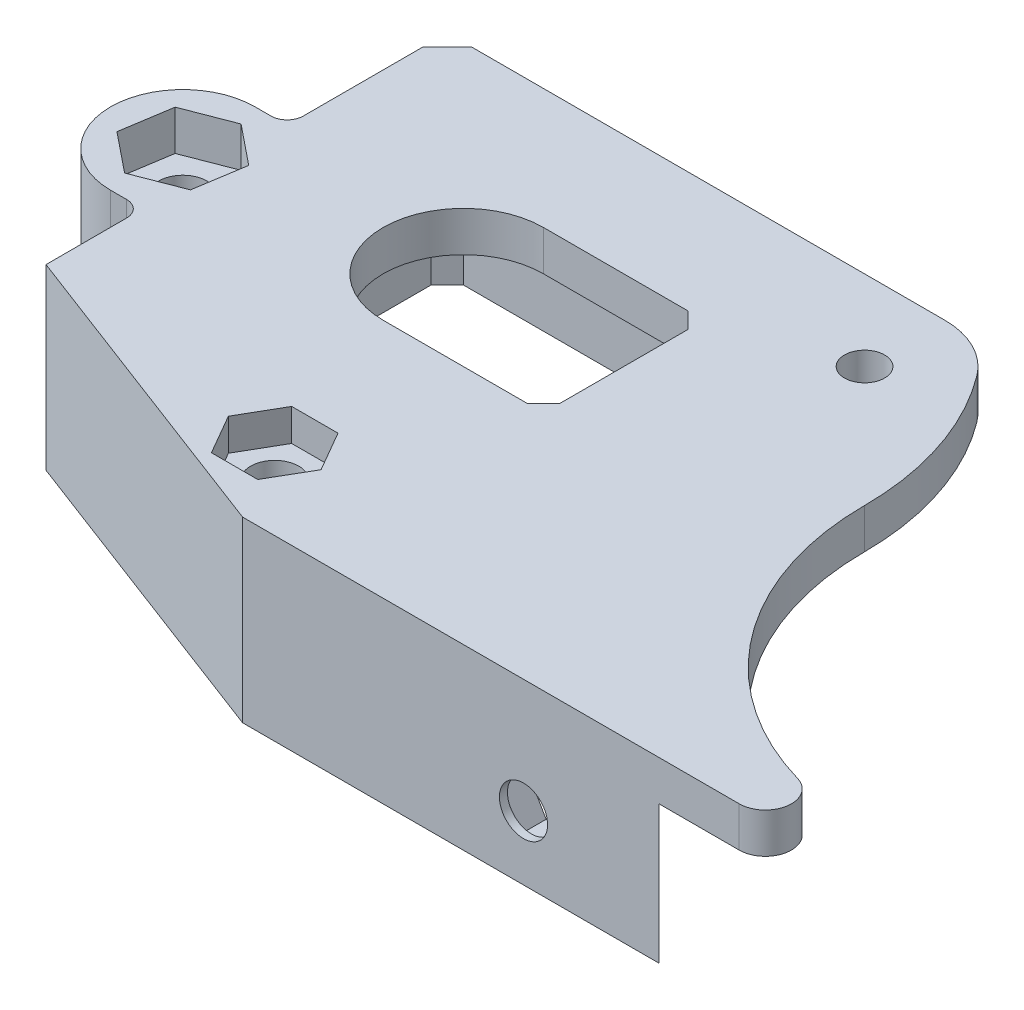
SolidWorks part; units mm, degrees
ref_plane "Front Plane" through (0, 0, 0) normal (0, 0, 1) x (1, 0, 0)
ref_plane "Top Plane" through (0, 0, 0) normal (0, 1, 0) x (1, 0, 0)
ref_plane "Right Plane" through (0, 0, 0) normal (1, 0, 0) x (0, 0, -1)
sketch "Sketch2" plane through (0, 0, 0) normal (0, 1, 0) x (1, 0, 0)
  line L0 (0, -40) -> (-72.5, -40) construction
  line L6 (-112, 25) -> (-112, -25)
  line L9 (-72.5, -40) -> (-20.6155, -40)
  line L10 (-102, 21) -> (-60, 21) construction
  line L11 (-102, 21) -> (-102, -21) construction
  line L12 (-102, -21) -> (-60, -21) construction
  line L13 (-60, 21) -> (-60, -21) construction
  line L14 (-102, 21) -> (-60, -21) construction
  line L21 (-102, -21) -> (-60, 21) construction
  line L22 (-29.4788, -34) -> (-77.0327, -34)
  line L23 (-108, -22.2403) -> (-108, 21)
  line L24 (-108, 21) -> (-60, 21)
  line L25 (-72.5, -40) -> (-112, -25)
  line L26 (-77.0327, -34) -> (-108, -22.2403)
  line L27 (-112, 25) -> (-56, 25)
  arc A2 (-22.016, 33.3961) -> (0, -40) centre (0, 0) cw construction
  arc A3 (-22.016, 33.3961) -> (-60, 21) centre (-63.6326, 96.5245) cw construction
  circle A8 centre (0, 0) radius 40 construction
  arc A9 (-20.6155, -40) -> (-29.4788, -34) centre (0, 0) cw
  circle A10 centre (-50, 15) radius 11 construction
  arc A11 (-60, 21) -> (-56, 25) centre (-50, 15) cw
  point P9 (-81, 0)
  point P20 (-112, 0)
  dimension "D1" = 40
  dimension "D2" = 72.5
  dimension "D6" = 45
  dimension "D11" = 15
  dimension "D14" = 4
  dimension "D9" = 22
  dimension "D3" = 42
  dimension "D4" = 42
  dimension "D5" = 81
  dimension "D7" = 6
  dimension "D8" = 4
  dimension "D10" = 50
  dimension "D12" = 4
  dimension "D13" = 50
  dimension "D15" = 52
extrude "Boss-Extrude1" add sketch "Sketch2" along normal blind 17.2
chamfer "Chamfer1" distance 3 angle 45 1 edges at (-112, 8.6, -25)
chamfer "Chamfer2" distance 2 angle 45 1 edges at (-108, 8.6, -21)
sketch "Sketch3" plane through (0, 17.2, 0) normal (0, 1, 0) x (1, 0, 0)
  line L0 (-85, 10) -> (-65, 10)
  line L1 (-72.5, -40) -> (-20.6155, -40)
  line L2 (-20.6155, -40) -> (-10.6155, -40)
  line L3 (-65, -10) -> (-85, -10)
  line L4 (-50, 25) -> (-109, 25)
  line L5 (-112, 22) -> (-112, -25)
  line L6 (-72.5, -40) -> (0, -40) construction
  line L7 (-112, -25) -> (-72.5, -40)
  line L8 (-109, 25) -> (-112, 22)
  line L9 (-65, 10) -> (-65, -10)
  circle A0 centre (-50, 15) radius 2.5
  arc A1 (0, -40) -> (-23.5728, 32.316) centre (0, 0) ccw construction
  arc A2 (-85, 10) -> (-85, -10) centre (-85, 0) ccw
  circle A3 centre (-78.5, -30) radius 3
  arc A4 (-35, 0) -> (-9.7132, -33.6252) centre (0, 0) ccw
  arc A5 (-35, 0) -> (-42, 21) centre (-70, 0) ccw
  arc A6 (-42, 21) -> (-50, 25) centre (-50, 15) ccw
  arc A7 (-10.6155, -40) -> (-9.7132, -33.6252) centre (-10.6155, -36.7487) ccw
  dimension "D1" = 5
  dimension "D2" = 40
  dimension "D3" = 35
  dimension "D5" = 6
  dimension "D8" = 10
  dimension "D4" = 10
  dimension "D6" = 30
  dimension "D7" = 85
  dimension "D9" = 20
  dimension "D10" = 78.5
extrude "Boss-Extrude2" add sketch "Sketch3" along normal blind 5
ref_axis "Axis1" through (0, 73.1015, 0) along (0, -1, 0)
sketch "Sketch5" plane through (0, 17.2, 0) normal (0, -1, 0) x (1, 0, 0)
  line L0 (-73.5, 30) -> (-73.5, 34)
  line L1 (-29.4788, 34) -> (-77.0327, 34) construction
  line L2 (-83.5, 30) -> (-83.5, 34)
  line L3 (-83.5, 34) -> (-73.5, 34)
  arc A1 (-83.5, 30) -> (-73.5, 30) centre (-78.5, 30) ccw
  circle A2 centre (-78.5, 30) radius 3
  dimension "D1" = 6
extrude "Boss-Extrude3" add sketch "Sketch5" along normal up to surface (17.2 mm away) up to face at (-80.921, 0, 5.1882)
sketch "Sketch7" plane through (0, 22.2, 0) normal (0, 1, 0) x (1, 0, 0)
  line L0 (-50, 25) -> (-109, 25) construction
  line L1 (-112, 22) -> (-112, -25) construction
  line L2 (-112, 5.05) -> (-112, -12.95)
  line L3 (-112, -12.95) -> (-116, -12.95)
  line L4 (-112, 5.05) -> (-116, 5.05)
  arc A0 (-116, 5.05) -> (-116, -12.95) centre (-116, -3.95) ccw
  dimension "D1" = 18
  dimension "D2" = 4
  dimension "D3" = 28.95
extrude "Boss-Extrude4" add sketch "Sketch7" against normal up to surface (22.2 mm away) up to face at (-80.5346, 0, 9.9202)
fillet "Fillet1" radius 2 2 edges at (-112, 11.1, 12.95) (-112, 11.1, -5.05)
sketch "Sketch8" plane through (0, 22.2, 0) normal (0, 1, 0) x (1, 0, 0)
  circle A0 centre (-116, -3.95) radius 3
  dimension "D1" = 6
extrude "Cut-Extrude3" cut sketch "Sketch8" against normal blind 31 contours A0
sketch "Sketch9" plane through (0, 22.2, 0) normal (0, 1, 0) x (1, 0, 0)
  line L1 (-110.0748, -1.6642) -> (-115.0169, 2.3243)
  line L2 (-115.0169, 2.3243) -> (-120.9422, 0.0385)
  line L3 (-120.9422, 0.0385) -> (-121.9252, -6.2358)
  line L4 (-121.9252, -6.2358) -> (-116.9831, -10.2243)
  line L5 (-116.9831, -10.2243) -> (-111.0578, -7.9385)
  line L6 (-111.0578, -7.9385) -> (-110.0748, -1.6642)
  circle A0 centre (-116, -3.95) radius 5.5 construction
  dimension "D1" = 11
extrude "Cut-Extrude4" cut sketch "Sketch9" against normal blind 5
sketch "Sketch10" plane through (0, 0, 40) normal (0, 0, 1) x (1, 0, 0)
  line L0 (-72.5, 0) -> (-20.6155, 0) construction
  circle A0 centre (-37.5, 8) radius 3
  dimension "D2" = 6
  dimension "D3" = 8
  dimension "D1" = 37.5
extrude "Cut-Extrude5" cut sketch "Sketch10" against normal blind 44 contours A0
fillet "Fillet2" radius 2 2 edges at (-83.5, 8.6, 31.5441) (-73.5, 8.6, 34)
chamfer "Chamfer3" distance 2 angle 45 2 edges at (-65, 19.7, -10) (-65, 19.7, 10)
sketch "Sketch11" plane through (0, 22.2, 0) normal (0, 1, 0) x (1, 0, 0)
  line L1 (-72.7265, -30) -> (-75.6132, -25)
  line L2 (-75.6132, -25) -> (-81.3868, -25)
  line L3 (-81.3868, -25) -> (-84.2735, -30)
  line L4 (-84.2735, -30) -> (-81.3868, -35)
  line L5 (-81.3868, -35) -> (-75.6132, -35)
  line L6 (-75.6132, -35) -> (-72.7265, -30)
  circle A0 centre (-78.5, -30) radius 5 construction
  dimension "D1" = 10
extrude "Cut-Extrude6" cut sketch "Sketch11" against normal blind 4
sketch "Sketch12" plane through (0, 0, 34) normal (0, 0, -1) x (-1, 0, 0)
  line L1 (43.8509, 8) -> (40.6754, 13.5)
  line L2 (40.6754, 13.5) -> (34.3246, 13.5)
  line L3 (34.3246, 13.5) -> (31.1491, 8)
  line L4 (31.1491, 8) -> (34.3246, 2.5)
  line L5 (34.3246, 2.5) -> (40.6754, 2.5)
  line L6 (40.6754, 2.5) -> (43.8509, 8)
  circle A0 centre (37.5, 8) radius 5.5 construction
  dimension "D1" = 11
extrude "Cut-Extrude7" cut sketch "Sketch12" against normal blind 5
